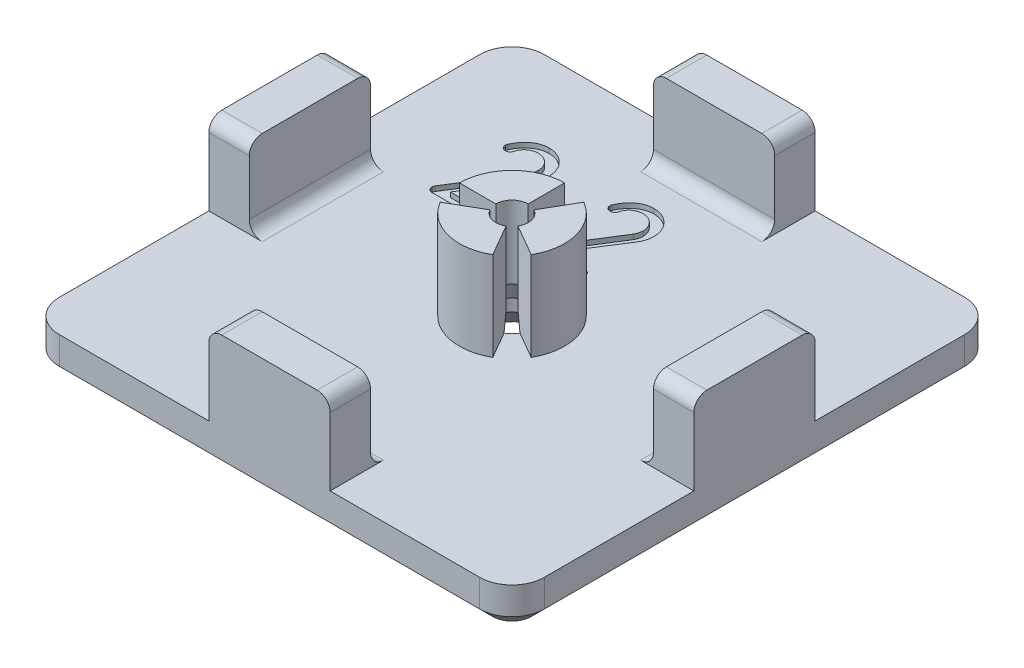
SolidWorks part; units mm, degrees
note: '?' marks a value the reader was unsure of.
ref_plane "Front Plane" through (0, 0, 0) normal (0, 0, 1) x (1, 0, 0)
ref_plane "Top Plane" through (0, 0, 0) normal (0, 1, 0) x (1, 0, 0)
ref_plane "Right Plane" through (0, 0, 0) normal (1, 0, 0) x (0, 0, -1)
sketch "Sketch2" plane through (0, 0, 0) normal (0, 1, 0) x (1, 0, 0)
  line L1 (-15, -15) -> (15, -15)
  line L2 (-15, -15) -> (-15, 15)
  line L3 (-15, 15) -> (15, 15)
  line L4 (15, -15) -> (15, 15)
  line L5 (-15, -15) -> (15, 15) construction
  line L6 (-15, 15) -> (15, -15) construction
  point P0 (0, 0)
  dimension "D1" = 30
extrude "extrude main face" add sketch "Sketch2" along normal blind 2.5
ref_axis "Axis1" through (0, 8.5586, 0) along (0, -1, 0)?
fillet "Fillet1" radius 2 4 edges at (15, 1.25, -15) (-15, 1.25, -15) (-15, 1.25, 15) (15, 1.25, 15)
chamfer "chamfer bottom" distance 0.8 angle 45 8 edges at (0, 0, -15) (-14.4142, 0, -14.4142) (14.4142, 0, -14.4142) (-15, 0, 0) (15, 0, 0) (-14.4142, 0, 14.4142) (14.4142, 0, 14.4142) (0, 0, 15)
sketch "Sketch3" plane through (0, 2.5, 0) normal (0, 1, 0) x (1, 0, 0)
  circle A0 centre (0, 0) radius 3.25
  dimension "D1" = 6.5
extrude "center peg" add sketch "Sketch3" along normal blind 5.5
sketch "Sketch7" plane through (0, 2.5, 0) normal (0, 1, 0) x (1, 0, 0)
  line L0 (-15, 13) -> (-15, -13) construction
  line L1 (-15, 3.75) -> (-12.5, 3.75)
  line L2 (-15, 3.75) -> (-15, -3.75)
  line L3 (-15, -3.75) -> (-12.5, -3.75)
  line L4 (-12.5, 3.75) -> (-12.5, -3.75)
  point P6 (-12.5, 0)
  dimension "D1" = 2.5
  dimension "D2" = 7.5
extrude "Boss-Extrude1" add sketch "Sketch7" along normal blind 5
fillet "Fillet7" radius 0.8 3 edges at (-12.5, 2.5, 0) (-13.75, 7.5, -3.75) (-13.75, 7.5, 3.75)
pattern_circular "CirPattern6" count 4 over 360 about axis through (0, 0, 0) along (0, 1, 0) of "Fillet7", "Boss-Extrude1"
sketch "Sketch8" plane through (0, 0, 0) normal (0, 0, 1) x (1, 0, 0)
  line L0 (0, 0) -> (0, 8)
  line L1 (0, 8.5586) -> (0, -0.11) construction
  line L2 (0, 8) -> (1, 8)
  line L3 (3.25, 8) -> (-3.25, 8) construction
  line L4 (1, 8) -> (1, 3.5)
  line L5 (1, 3.5) -> (1.35, 2.5)
  line L6 (1.35, 2.5) -> (1.35, 0)
  line L7 (-13, 0) -> (13, 0) construction
  line L8 (1.35, 0) -> (0, 0)
  line L9 (0, 0) -> (0, 12.943) construction
  dimension "D1" = 2.7
  dimension "D2" = 2
  dimension "D3" = 2.5
  dimension "D4" = 1
revolve "Cut-Revolve1" cut sketch "Sketch8" angle 360 about L9
sketch "Sketch9" plane through (0, 8, 0) normal (0, 1, 0) x (1, 0, 0)
  line L0 (0, 0) -> (0, 3.25)
  line L1 (0, 0) -> (1.625, 2.8146)
  line L22 (-3.75, -15) -> (-3.75, -11.7)
  line L23 (-3.75, -11.7) -> (3.75, -11.7)
  line L24 (3.75, -11.7) -> (3.75, -15)
  line L25 (3.75, -15) -> (13, -15)
  line L26 (15, -13) -> (15, -3.75)
  line L27 (15, -3.75) -> (11.7, -3.75)
  line L28 (11.7, -3.75) -> (11.7, 3.75)
  line L29 (11.7, 3.75) -> (15, 3.75)
  line L30 (15, 3.75) -> (15, 13)
  line L31 (13, 15) -> (3.75, 15)
  line L32 (3.75, 15) -> (3.75, 11.7)
  line L33 (3.75, 11.7) -> (-3.75, 11.7)
  line L34 (-3.75, 11.7) -> (-3.75, 15)
  line L35 (-3.75, 15) -> (-13, 15)
  line L36 (-15, 13) -> (-15, 3.75)
  line L37 (-15, 3.75) -> (-11.7, 3.75)
  line L38 (-11.7, 3.75) -> (-11.7, -3.75)
  line L39 (-11.7, -3.75) -> (-15, -3.75)
  line L40 (-15, -3.75) -> (-15, -13)
  line L41 (-13, -15) -> (-3.75, -15)
  line L42 (-3.75, -15) -> (-3.75, -11.7)
  line L43 (-3.75, -11.7) -> (3.75, -11.7)
  line L44 (3.75, -11.7) -> (3.75, -15)
  line L45 (3.75, -15) -> (13, -15)
  line L46 (15, -13) -> (15, -3.75)
  line L47 (15, -3.75) -> (11.7, -3.75)
  line L48 (11.7, -3.75) -> (11.7, 3.75)
  line L49 (11.7, 3.75) -> (15, 3.75)
  line L50 (15, 3.75) -> (15, 13)
  line L51 (13, 15) -> (3.75, 15)
  line L52 (3.75, 15) -> (3.75, 11.7)
  line L53 (3.75, 11.7) -> (-3.75, 11.7)
  line L54 (-3.75, 11.7) -> (-3.75, 15)
  line L55 (-3.75, 15) -> (-13, 15)
  line L56 (-15, 13) -> (-15, 3.75)
  line L57 (-15, 3.75) -> (-11.7, 3.75)
  line L58 (-11.7, 3.75) -> (-11.7, -3.75)
  line L59 (-11.7, -3.75) -> (-15, -3.75)
  line L60 (-15, -3.75) -> (-15, -13)
  line L61 (-13, -15) -> (-3.75, -15)
  circle A0 centre (0, 0) radius 3.25 construction
  circle A2 centre (0, 0) radius 3.25 construction
  arc A3 (1.625, 2.8146) -> (0, 3.25) centre (0, 0) ccw
  arc A6 (13, -15) -> (15, -13) centre (13, -13) ccw
  arc A7 (15, 13) -> (13, 15) centre (13, 13) ccw
  arc A8 (-13, 15) -> (-15, 13) centre (-13, 13) ccw
  arc A9 (-15, -13) -> (-13, -15) centre (-13, -13) ccw
  arc A10 (13, -15) -> (15, -13) centre (13, -13) ccw
  arc A11 (15, 13) -> (13, 15) centre (13, 13) ccw
  arc A12 (-13, 15) -> (-15, 13) centre (-13, 13) ccw
  arc A13 (-15, -13) -> (-13, -15) centre (-13, -13) ccw
  dimension "D1" = 30
  dimension "D2" = 0
extrude "cut cylinder notch" cut sketch "Sketch9" against normal up to surface (5.5 mm away) contours L0 A3 L1 up to face at (0, 2.5, 3.25)
pattern_circular "CirPattern7" count 3 over 360 about axis through (0, 0, 0) along (0, 1, 0) of "cut cylinder notch"
chamfer "chamf screwHole" distance 1.75 angle 45 1 edges at (0, 0, -1.35)
sketch "Sketch5" plane through (0, 0, 0) normal (0, 0, 1) x (1, 0, 0)
  line L0 (-7.45, 2.5) -> (-5.55, 6.5)
  line L1 (-13, 2.5) -> (-3.75, 2.5) construction
  line L2 (-5.55, 6.5) -> (-6.55, 10.5)
  line L3 (-6.55, 10.5) -> (-8.6116, 10.5)
  line L4 (-8.6116, 10.5) -> (-7.6642, 6.7105)
  line L5 (-7.6642, 6.7105) -> (-9.6642, 2.5)
  line L6 (-9.6642, 2.5) -> (-7.45, 2.5)
  line L7 (-5.95, 2.5) -> (-5.95, 10.5) construction
  line L8 (-5.95, 10.5) -> (0, 10.5) construction
  line L9 (0, 10.5) -> (0, 0) construction
  dimension "D1" = 5.95
  dimension "D2" = 0.4
  dimension "D3" = 8
  dimension "D4" = 1.5
  dimension "D5" = 2
  dimension "D6" = 0.6
  dimension "D7" = 4
  dimension "D8" = 2
ref_plane "Plane1" through (0, 6.5, 0) normal (0, 1, 0) x (1, 0, 0)
sketch "Sketch10" plane through (0, 2.5, 0) normal (0, 1, 0) x (1, 0, 0)
  text T0 "2.2\r\n" font "DS ISO 1" height 6
extrude "cut version Number" cut sketch "Sketch10" against normal blind 0.3
equation "\"D8@Sketch5\"=\"D5@Sketch5\""
